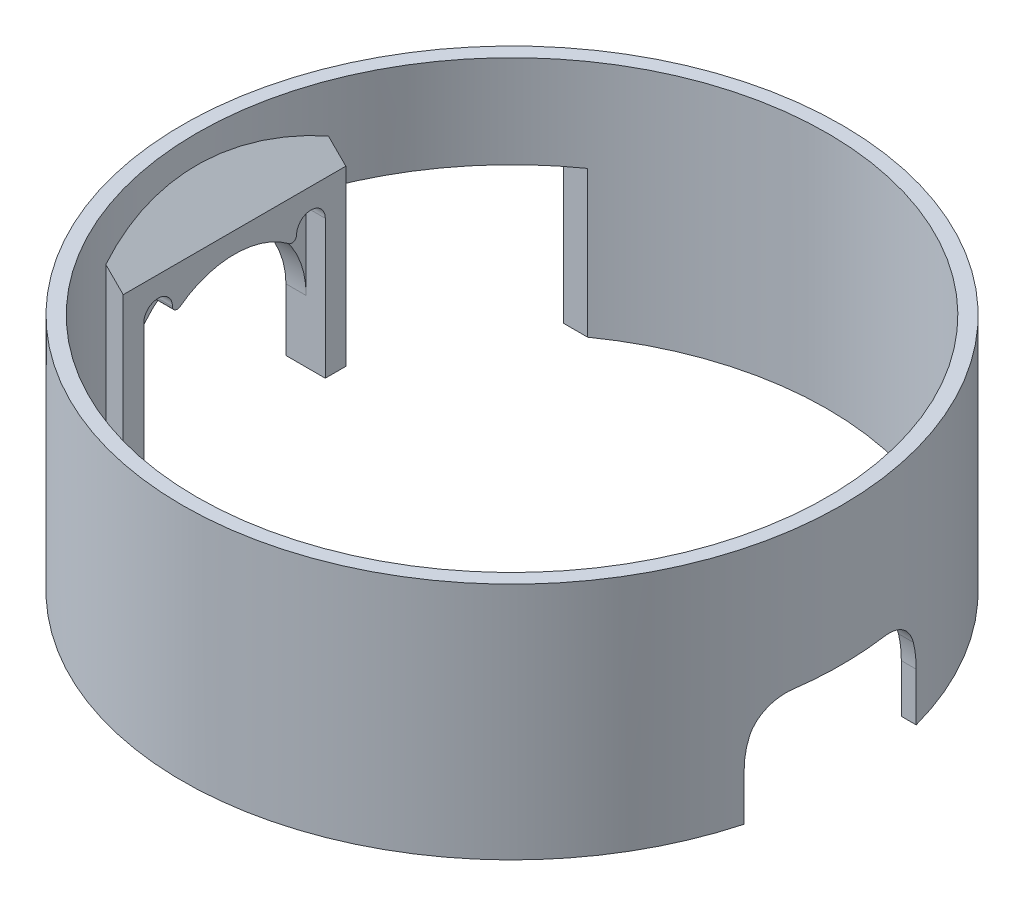
SolidWorks part; units mm, degrees
ref_plane "Front Plane" through (0, 0, 0) normal (0, 0, 1) x (1, 0, 0)
ref_plane "Top Plane" through (0, 0, 0) normal (0, 1, 0) x (1, 0, 0)
ref_plane "Right Plane" through (0, 0, 0) normal (1, 0, 0) x (0, 0, -1)
sketch "Sketch1" plane through (0, 0, 0) normal (0, 1, 0) x (1, 0, 0)
  circle A0 centre (0, 0) radius 69
  circle A1 centre (0, 0) radius 66
  dimension "D1" = 138
  dimension "D2" = 3
extrude "Boss-Extrude1" add sketch "Sketch1" along normal blind 50
sketch "Sketch4" plane through (0, 0, 0) normal (1, 0, 0) x (0, 0, -1)
  line L1 (23.3, 0) -> (53.9, 0)
  line L2 (23.3, 0) -> (23.3, 30.6)
  line L3 (23.3, 30.6) -> (53.9, 30.6)
  line L4 (53.9, 0) -> (53.9, 30.6)
  dimension "D1" = 30.6
  dimension "D2" = 30.6
  dimension "D3" = 0
  dimension "D4" = 23.3
extrude "Cut-Extrude2" cut sketch "Sketch4" against normal through all
sketch "Sketch5" plane through (0, 0, 0) normal (1, 0, 0) x (0, 0, -1)
  line L8 (19, 13) -> (19, -6)
  line L9 (19, -6) -> (-19, -6)
  line L10 (-19, -6) -> (-19, 13)
  arc A1 (19, 13) -> (-19, 13) centre (0, 13) ccw
  dimension "D1" = 19
  dimension "D3" = 13
  dimension "D2" = 19
extrude "Cut-Extrude6" cut sketch "Sketch5" against normal through all
sketch "Sketch6" plane through (0, 0, 0) normal (1, 0, 0) x (0, 0, -1)
  line L0 (19, 13) -> (19, 0)
  line L2 (-19, 0) -> (-19, 13)
  line L3 (23.3, 13) -> (23.3, 0)
  line L4 (-23.3, 0) -> (-23.3, 13)
  line L5 (23.3, 0) -> (19, 0)
  line L6 (-19, 0) -> (-23.3, 0)
  arc A0 (19, 13) -> (-19, 13) centre (0, 13) ccw
  arc A1 (23.3, 13) -> (-23.3, 13) centre (0, 13) ccw
  dimension "D1" = 19
  dimension "D3" = 0
  dimension "D2" = 4.3
extrude "Boss-Extrude2" add sketch "Sketch6" against normal up to next from offset 58.1 offset against normal yes
sketch "Sketch7" plane through (-58.1, 0, 0) normal (1, 0, 0) x (0, 0, -1)
  line L0 (0, 36.3) -> (15, 36.3) construction
  arc A0 (23.3, 13) -> (-23.3, 13) centre (0, 13) ccw construction
  dimension "D1" = 15
ref_plane "Plane2" through (-10.9, -10.9, 0) normal (-0.7071, -0.7071, 0) x (0, 0, -1)
sketch "Sketch8" plane through (-10.9, -10.9, 0) normal (-0.7071, -0.7071, 0) x (0, 0, -1)
  line L0 (23.3, -41.0829) -> (23.3, -50.2753) construction
  line L1 (-23.3, -84.0829) -> (23.3, -84.0829)
  line L2 (-23.3, -84.0829) -> (-23.3, -49.0829)
  line L3 (-23.3, -49.0829) -> (23.3, -49.0829)
  line L4 (23.3, -84.0829) -> (23.3, -49.0829)
  line L5 (-23.3, -50.2753) -> (-23.3, -41.0829) construction
  line L6 (19, -41.0829) -> (23.3, -41.0829) construction
  dimension "D1" = 0
  dimension "D2" = 0
  dimension "D3" = 8
  dimension "D4" = 35
extrude "Boss-Extrude4" add sketch "Sketch8" along normal blind 30 contours L2 L1 L4 L3
sketch "Sketch9" plane through (0, 0, 0) normal (0, -1, 0) x (1, 0, 0)
  line L0 (-58.1, -23.3) -> (-61.7504, -23.3)
  line L1 (-64.947, -23.3) -> (-58.1, -23.3) construction
  line L6 (-38.0892, -53.9) -> (-43.0789, -53.9)
  line L7 (-38.0892, -53.9) -> (-43.0789, -53.9)
  line L12 (-66.3325, 19) -> (-58.1, 19)
  line L14 (-58.1, 19) -> (-58.1, 23.3)
  line L15 (-58.1, 23.3) -> (-61.7504, 23.3)
  line L18 (-58.1, 19) -> (-58.1, 23.3)
  line L19 (-58.1, 23.3) -> (-61.7504, 23.3)
  line L20 (-58.1, 19) -> (-58.1, -19)
  line L24 (-58.1, -19) -> (-66.3325, -19)
  line L25 (-64.947, -23.3) -> (-58.1, -23.3)
  line L27 (-58.1, -23.3) -> (-58.1, -19)
  line L31 (-58.1, -23.3) -> (-58.1, -19)
  arc A6 (-43.0789, -53.9) -> (-66.3325, 19) centre (0, 0) ccw
  arc A7 (-38.0892, -53.9) -> (-61.7504, 23.3) centre (0, 0) ccw
  arc A8 (-43.0789, -53.9) -> (-66.3325, 19) centre (0, 0) ccw
  arc A9 (-38.0892, -53.9) -> (-61.7504, 23.3) centre (0, 0) ccw
  arc A10 (-66.3325, -19) -> (-66.3325, 19) centre (0, 0) ccw
  arc A11 (-61.7504, -23.3) -> (-61.7504, 23.3) centre (0, 0) ccw
  arc A12 (-66.3325, -19) -> (-64.947, -23.3) centre (0, 0) ccw
  arc A14 (-66.3325, -19) -> (-64.947, -23.3) centre (0, 0) ccw
  circle A16 centre (0, 0) radius 69
  arc A18 (-61.7504, -23.3) -> (-61.7504, 23.3) centre (0, 0) ccw
  line M15 (-66.3325, 19) -> (-58.1, 19)
  line M16 (-58.1, 19) -> (-58.1, 23.3)
  line M17 (-58.1, 23.3) -> (-61.7504, 23.3)
  arc M18 (-61.7504, 23.3) -> (-38.0892, -53.9) centre (0, 0) cw
  dimension "D1" = 0
  dimension "D2" = 0
extrude "Cut-Extrude7" cut sketch "Sketch9" against normal through all flip side to cut contours A16
extrude "Cut-Extrude8" cut sketch "Sketch9<3>" against normal through all contours L31 A11 M15 M18 M17 M16 region at (1.3919, 0, 0)
sketch "Sketch9<3>" plane through (0, 0, 0) normal (0, -1, 0) x (1, 0, 0) same geometry as "Sketch9"
extrude "Cut-Extrude9" cut sketch "Sketch5<2>" against normal through all
sketch "Sketch5<2>" plane through (0, 0, 0) normal (1, 0, 0) x (0, 0, -1) same geometry as "Sketch5"
sketch "Sketch11" plane through (-58.1, 0, 0) normal (1, 0, 0) x (0, 0, -1)
  line L0 (-19, 29) -> (-19, 11)
  line L1 (-19, 0) -> (-19, 13) construction
  line L2 (-19, 11) -> (-13, 11)
  line L3 (-13, 11) -> (-13, 29)
  line L4 (13, 29) -> (13, 11)
  line L5 (19, 29) -> (19, 11)
  line L6 (19, 13) -> (19, 0) construction
  line L7 (13, 11) -> (19, 11)
  arc A0 (19, 29) -> (13, 29) centre (16, 29) ccw
  arc A1 (-13, 29) -> (-19, 29) centre (-16, 29) ccw
  dimension "D1" = 6
  dimension "D2" = 6
  dimension "D3" = 18
  dimension "D4" = 18
extrude "Cut-Extrude11" cut sketch "Sketch11" against normal blind 4
fillet "Fillet3" radius 1 2 edges at (-60.1, 26.8564, -13) (-60.1, 26.8564, 13)
sketch "Sketch12" plane through (0, 0, 0) normal (1, 0, 0) x (0, 0, -1)
  line L25 (-18, -0.9) -> (18, -0.9)
  line L28 (18, -0.9) -> (18, 10.1)
  line L29 (9.5394, 21.1) -> (-9.5394, 21.1)
  line L30 (-18, 10.1) -> (-18, -0.9)
  line L31 (18, -0.9) -> (18, 10.1)
  line L32 (9.5394, 21.1) -> (-9.5394, 21.1)
  line L33 (-18, 10.1) -> (-18, -0.9)
  arc A34 (18, 10.1) -> (17.1709, 15.5) centre (0, 10.1) ccw
  arc A35 (17.1709, 15.5) -> (9.5394, 21.1) centre (9.5394, 13.1) ccw
  arc A36 (-9.5394, 21.1) -> (-17.1709, 15.5) centre (-9.5394, 13.1) ccw
  arc A37 (-17.1709, 15.5) -> (-18, 10.1) centre (0, 10.1) ccw
  arc A38 (18, 10.1) -> (17.1709, 15.5) centre (0, 10.1) ccw
  arc A39 (17.1709, 15.5) -> (9.5394, 21.1) centre (9.5394, 13.1) ccw
  arc A40 (-9.5394, 21.1) -> (-17.1709, 15.5) centre (-9.5394, 13.1) ccw
  arc A41 (-17.1709, 15.5) -> (-18, 10.1) centre (0, 10.1) ccw
  dimension "D1" = 0
extrude "Cut-Extrude12" cut sketch "Sketch12" along normal through all
